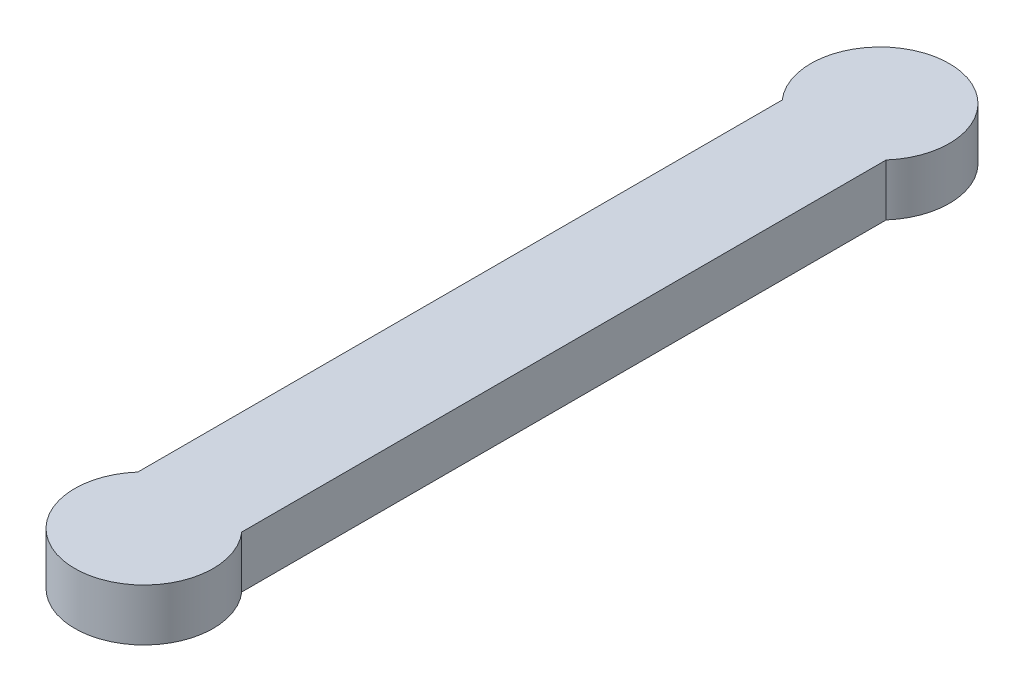
SolidWorks part; units mm, degrees
ref_plane "Front Plane" through (0, 0, 0) normal (0, 0, 1) x (1, 0, 0)
ref_plane "Top Plane" through (0, 0, 0) normal (0, 1, 0) x (1, 0, 0)
ref_plane "Right Plane" through (0, 0, 0) normal (1, 0, 0) x (0, 0, -1)
sketch "Sketch1" plane through (0, 0, 0) normal (0, 1, 0) x (1, 0, 0)
  line L0 (0, 0) -> (0, 51.8396) construction
  line L1 (-3, 39.8542) -> (-3, 2.6458)
  line L2 (3, 39.8542) -> (3, 2.6458)
  arc A0 (-3, 2.6458) -> (3, 2.6458) centre (0, 0) ccw
  arc A1 (3, 39.8542) -> (-3, 39.8542) centre (0, 42.5) ccw
  dimension "D2" = 8
  dimension "D3" = 8
  dimension "D1" = 42.5
  dimension "D4" = 3
extrude "Boss-Extrude1" add sketch "Sketch1" along normal blind 3
